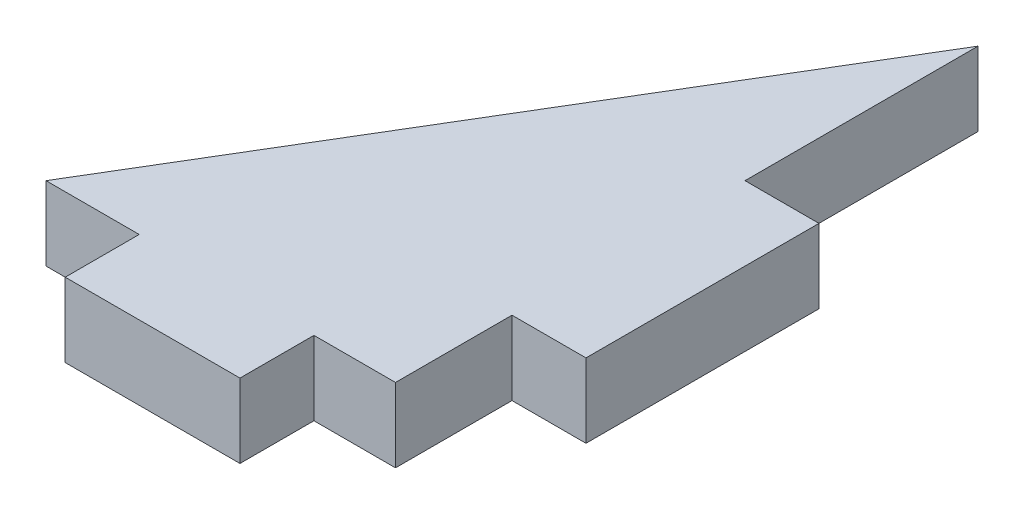
SolidWorks part; units mm, degrees
material "ABS"
ref_plane "Plan de face" through (0, 0, 0) normal (0, 0, 1) x (1, 0, 0)
ref_plane "Plan de dessus" through (0, 0, 0) normal (0, 1, 0) x (1, 0, 0)
ref_plane "Plan de droite" through (0, 0, 0) normal (1, 0, 0) x (0, 0, -1)
sketch "Esquisse1" plane through (0, 0, 0) normal (0, 1, 0) x (1, 0, 0)
  line L0 (-30, 0) -> (0, 0)
  line L1 (0, 0) -> (0, 50)
  line L2 (0, 50) -> (-30, 0)
  line L3 (-55, 0) -> (55, 0) construction
  dimension "D1" = 50
  dimension "D2" = 30
extrude "Boss.-Extru.1" add sketch "Esquisse1" along normal blind 6.35
sketch "Esquisse2" plane through (0, 0, 0) normal (1, 0, 0) x (0, 0, -1)
  line L0 (0, 6.35) -> (50, 6.35) construction
  line L1 (30, 6.35) -> (10, 6.35)
  line L2 (30, 6.35) -> (30, 0)
  line L3 (30, 0) -> (10, 0)
  line L4 (10, 6.35) -> (10, 0)
  line L5 (0, 0) -> (50, 0) construction
  line L6 (50, 6.35) -> (50, 0) construction
  dimension "D1" = 20
  dimension "D2" = 20
extrude "Boss.-Extru.2" add sketch "Esquisse2" along normal blind 6.35
sketch "Esquisse3" plane through (0, 0, 0) normal (0, 0, 1) x (1, 0, 0)
  line L0 (-30, 0) -> (0, 0) construction
  line L1 (-7, 0) -> (-22, 0)
  line L2 (-7, 0) -> (-7, 6.35)
  line L3 (-7, 6.35) -> (-22, 6.35)
  line L4 (-22, 0) -> (-22, 6.35)
  line L5 (-30, 6.35) -> (0, 6.35) construction
  line L6 (-30, 6.35) -> (-30, 0) construction
  dimension "D1" = 15
  dimension "D2" = 8
extrude "Boss.-Extru.3" add sketch "Esquisse3" along normal blind 6.35
